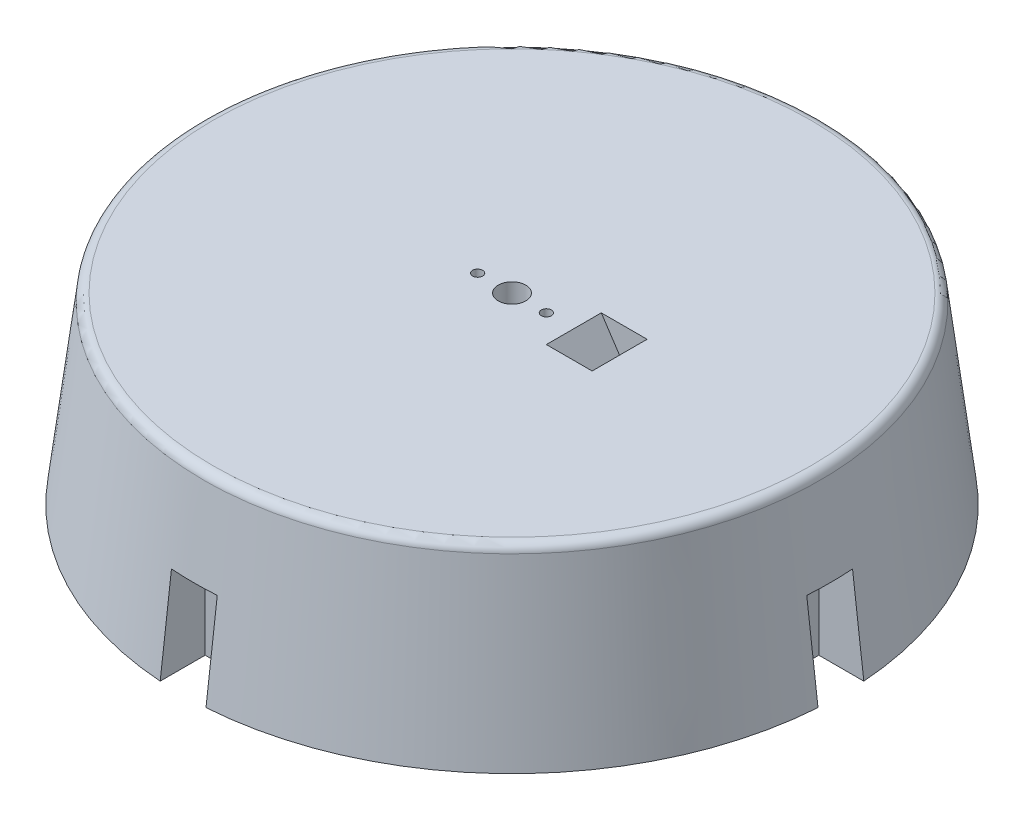
SolidWorks part; units mm, degrees
material "ABS PC"
ref_plane "Plan de face" through (0, 0, 0) normal (0, 0, 1) x (1, 0, 0)
ref_plane "Plan de dessus" through (0, 0, 0) normal (0, 1, 0) x (1, 0, 0)
ref_plane "Plan de droite" through (0, 0, 0) normal (1, 0, 0) x (0, 0, -1)
sketch "Esquisse3" plane through (0, 0, 0) normal (0, 1, 0) x (1, 0, 0)
  circle A0 centre (0, 0) radius 72
  dimension "D1" = 144
extrude "Boss.-Extru.1" add sketch "Esquisse3" along normal blind 40 draft 7
fillet "Congé2" radius 2 1 edges at (0, 40, 67.0886)
sketch "Esquisse26" plane through (0, 0, 0) normal (0, -1, 0) x (-1, 0, 0)
  circle A1 centre (0, 0) radius 20 construction
  circle A3 centre (0, 0) radius 7.5
  dimension "D1" = 40
  dimension "D4" = 15
extrude "Enlèv. mat.-Extru.1" cut sketch "Esquisse26" against normal blind 4
sketch "Esquisse27" [suppressed] plane through (0, 0, 0) normal (0, -1, 0) x (1, 0, 0)
  line L0 (0, 0) -> (84.4078, 0) construction
  line L1 (0, 0) -> (0, 67.4941) construction
  line L2 (99.7787, 6.6489) -> (93.792, 6.25)
  line L3 (99.7787, -6.6489) -> (93.792, -6.25)
  circle A0 centre (0, 0) radius 100 construction
  arc A1 (99.7787, -6.6489) -> (99.7787, 6.6489) centre (0, 0) ccw
  arc A2 (93.792, -6.25) -> (93.792, 6.25) centre (0, 0) ccw
  circle A4 centre (0, 0) radius 94 construction
  circle A5 centre (0, 0) radius 100 construction
  point P8 (52.5968, 16.0804)
  point P13 (52, 0)
  dimension "D2" = 12.5
  dimension "D1" = 6
extrude "Boss.-Extru.14" [suppressed] add sketch "Esquisse27" along normal blind 30
ref_plane "Plan1" [suppressed] through (93.792, 0, 0) normal (1, 0, 0) x (0, 0, -1)
sketch "Esquisse29" [suppressed] plane through (93.792, 0, 0) normal (1, 0, 0) x (0, 0, -1)
  line L0 (6.25, -30) -> (6.25, 0) construction
  line L1 (-6.25, -30) -> (-6.25, 0) construction
  line L2 (6.25, -24.317) -> (6.25, 0) construction
  line L3 (-6.25, -33.1717) -> (-6.25, 0) construction
  line L4 (-6.25, -30) -> (6.25, -30) construction
  line L5 (-6.25, -30) -> (6.25, -30) construction
  line L6 (0, -30) -> (0, -24.1817) construction
  circle A0 centre (0, -26) radius 4
  dimension "D1" = 8
extrude "Boss.-Extru.15" [suppressed] add sketch "Esquisse29" along normal blind 2 and the other way blind 8 draft 1
fillet "Congé7" [suppressed] radius 2
pattern_circular "Répétition circulaire4" [suppressed] count 4 over 360 of bodies 123
sketch "Esquisse39" plane through (0, 0, 0) normal (0, -1, 0) x (1, 0, 0)
  line L0 (0, 0) -> (72, 0) construction
  line L1 (72, -5) -> (72, 5)
  line L2 (72, 5) -> (62, 5)
  line L4 (72, -5) -> (62, -5)
  line L5 (62, 5) -> (62, -5)
  line L6 (72, 5) -> (62, -5) construction
  line L7 (72, -5) -> (62, 5) construction
  circle A0 centre (0, 0) radius 72 construction
  circle A2 centre (0, 0) radius 67 construction
  point P3 (67, 0)
  dimension "D2" = 134
  dimension "D1" = 10
extrude "Enlèv. mat.-Extru.4" cut sketch "Esquisse39" against normal blind 20
sketch "Esquisse40" plane through (62, 0, 0) normal (1, 0, 0) x (0, 0, -1)
  line L0 (0, 0) -> (0, 10) construction
  line L1 (-5, 0) -> (5, 0) construction
  line L2 (-5, 10) -> (5, 10) construction
  line L3 (-5, 20) -> (-5, 0) construction
  line L4 (5, 20) -> (5, 0) construction
  circle A0 centre (0, 5) radius 2.1643
  circle A1 centre (0, 15) radius 2.1643
hole_wizard "Dégagement M2.51" positions "Esquisse41" profile "Esquisse42" hole size "M2.5" standard "ISO"
sketch "Esquisse41" plane through (62, 0, 0) normal (1, 0, 0) x (0, 0, -1)
  point P0 (0, 15)
  point P3 (0, 5)
sketch "Esquisse42" plane through (62, 15, 0) normal (0, 1, 0) x (0, 0, -1)
  line L0 (0, 0) -> (0, 4.8112)
  line L1 (0, 4.8112) -> (1.35, 4)
  line L2 (1.35, 4) -> (1.35, 0)
  line L5 (1.35, 0) -> (0, 0)
  line L10 (0, 4.8112) -> (-1.35, 4) construction
  line L11 (0, -6.35) -> (0, 107.95) construction
  dimension "Diamètre du perçage" = 2.7
  dimension "Profondeur du perçage" = 4
  dimension "Angle de pointe" = 118
pattern_circular "Répétition circulaire5" count 4 every 90 about axis through (0, 4, 0) along (0, -1, 0) of "Enlèv. mat.-Extru.4", "Dégagement M2.51"
sketch "Esquisse30" plane through (0, 40, 0) normal (0, 1, 0) x (1, 0, 0)
  line L0 (0, 0) -> (0, 72.707) construction
  line L1 (0, 0) -> (85.5223, 0) construction
  line L2 (7.5, 0) -> (-7.5, 0)
  circle A0 centre (0, 0) radius 3
  dimension "D2" = 6
  dimension "D1" = 15
ref_axis "Axe1" through (0, 117.1902, 0) along (0, -1, 0)
hole_wizard "Dégagement M21" positions "Esquisse31" profile "Esquisse32" hole size "M2" standard "ISO"
sketch "Esquisse31" plane through (0, 40, 0) normal (0, 1, 0) x (1, 0, 0)
  line L2 (0, 0) -> (0, 24.4674) construction
  line L4 (-7.5, 0) -> (7.5, 0) construction
  point P29 (-7.5, 0)
  point P30 (7.5, 0)
  point P32 (0, 0)
  dimension "D1" = 15
sketch "Esquisse32" plane through (7.5, 40, 0) normal (1, 0, 0) x (0, 0, 1)
  line L0 (0, 0) -> (0, 7.6609)
  line L1 (0, 7.6609) -> (1.1, 7)
  line L2 (1.1, 7) -> (1.1, 0)
  line L5 (1.1, 0) -> (0, 0)
  line L10 (0, 7.6609) -> (-1.1, 7) construction
  line L11 (0, -6.35) -> (0, 107.95) construction
  dimension "Diamètre du perçage" = 2.2
  dimension "Profondeur du perçage" = 7
  dimension "Angle de pointe" = 118
extrude "Enlèv. mat.-Extru.2" cut sketch "Esquisse30" against normal blind 15 contours L2 A0 | L2 A0 region at (0, 40, 1.2732) region at (0, 40, -1.2732)
sketch "Esquisse33" plane through (0, 25, 0) normal (0, 1, 0) x (1, 0, 0)
  line L0 (0, 0) -> (0, 41.3983) construction
  circle A0 centre (0, 0) radius 2
  dimension "D1" = 4
extrude "Enlèv. mat.-Extru.3" cut sketch "Esquisse33" against normal through all
sketch "Esquisse34" plane through (0, 40, 0) normal (0, 1, 0) x (1, 0, 0)
  line L0 (0, 0) -> (65.3192, 0) construction
  line L1 (0, 0) -> (0, 65.3192) construction
  line L2 (13.5, 6) -> (13.5, -6)
  line L3 (13.5, -6) -> (23.5, -6)
  line L4 (23.5, -6) -> (23.5, 6)
  line L5 (23.5, 6) -> (13.5, 6)
  circle A0 centre (0, 0) radius 65.3192 construction
  point P11 (13.5, 0)
  dimension "D1" = 10
  dimension "D2" = 12
  dimension "D3" = 13.5
sketch "Esquisse36" plane through (0, 0, 0) normal (0, -1, 0) x (1, 0, 0)
  line L0 (0, 0) -> (40, 0) construction
  line L9 (50, -6) -> (50, 6)
  line L10 (40, -6) -> (50, -6)
  line L11 (40, 6) -> (40, -6)
  line L12 (50, 6) -> (40, 6)
  line L13 (13.5, -6) -> (13.5, 6) construction
  line L14 (13.5, 6) -> (23.5, 6) construction
  dimension "D1" = 40
ref_plane "Plan2" through (27.7989, 18.4168, 0) normal (0.8336, 0.5523, 0) x (0, 0, -1)
ref_plane "Plan3" through (34.7486, 23.021, 0) normal (-0.8336, -0.5523, 0) x (0, 0, 1)
sketch "Esquisse37" plane through (27.7989, 18.4168, 0) normal (0.8336, 0.5523, 0) x (0, 0, -1)
  line L1 (6, 25.89) -> (-6, 25.89) construction
  line L3 (6, 25.89) -> (-6, 25.89)
  line L4 (6, 25.89) -> (6, -22.0917)
  line L6 (-6, -22.0917) -> (6, -22.0917) construction
  line L7 (-6, -22.0917) -> (6, -22.0917)
  line L8 (-6, 25.89) -> (-6, -22.0917)
extrude "Passage de cable" cut sketch "Esquisse36" along direction (0.5523, -0.8336, 0) on the side against the normal through all
sketch "Esquisse38" plane through (0, 0, 0) normal (0, -1, 0) x (-1, 0, 0)
  line L0 (0, 0) -> (0, 56.7481) construction
  line L17 (17.8293, 2.8513) -> (6.7498, 4.9083)
  line L18 (4.9083, 6.7498) -> (2.8513, 17.8293)
  line L19 (-2.8513, 17.8293) -> (-4.9083, 6.7498)
  line L20 (-6.7498, 4.9083) -> (-17.8293, 2.8513)
  line L21 (-17.8293, -2.8513) -> (-6.7498, -4.9083)
  line L22 (-4.9083, -6.7498) -> (-2.8513, -17.8293)
  line L23 (2.8513, -17.8293) -> (4.9083, -6.7498)
  line L24 (6.7498, -4.9083) -> (17.8293, -2.8513)
  line L25 (17.8293, 2.8513) -> (6.7498, 4.9083)
  line L26 (4.9083, 6.7498) -> (2.8513, 17.8293)
  line L27 (-2.8513, 17.8293) -> (-4.9083, 6.7498)
  line L28 (-6.7498, 4.9083) -> (-17.8293, 2.8513)
  line L29 (-17.8293, -2.8513) -> (-6.7498, -4.9083)
  line L30 (-4.9083, -6.7498) -> (-2.8513, -17.8293)
  line L31 (2.8513, -17.8293) -> (4.9083, -6.7498)
  line L32 (6.7498, -4.9083) -> (17.8293, -2.8513)
  arc A16 (17.8293, -2.8513) -> (17.8293, 2.8513) centre (17.3, 0) ccw
  arc A17 (4.9083, 6.7498) -> (6.7498, 4.9083) centre (7.1697, 7.1697) ccw
  arc A18 (2.8513, 17.8293) -> (-2.8513, 17.8293) centre (0, 17.3) ccw
  arc A19 (-6.7498, 4.9083) -> (-4.9083, 6.7498) centre (-7.1697, 7.1697) ccw
  arc A20 (-17.8293, 2.8513) -> (-17.8293, -2.8513) centre (-17.3, 0) ccw
  arc A21 (-4.9083, -6.7498) -> (-6.7498, -4.9083) centre (-7.1697, -7.1697) ccw
  arc A22 (-2.8513, -17.8293) -> (2.8513, -17.8293) centre (0, -17.3) ccw
  arc A23 (6.7498, -4.9083) -> (4.9083, -6.7498) centre (7.1697, -7.1697) ccw
  arc A24 (17.8293, -2.8513) -> (17.8293, 2.8513) centre (17.3, 0) ccw
  arc A25 (4.9083, 6.7498) -> (6.7498, 4.9083) centre (7.1697, 7.1697) ccw
  arc A26 (2.8513, 17.8293) -> (-2.8513, 17.8293) centre (0, 17.3) ccw
  arc A27 (-6.7498, 4.9083) -> (-4.9083, 6.7498) centre (-7.1697, 7.1697) ccw
  arc A28 (-17.8293, 2.8513) -> (-17.8293, -2.8513) centre (-17.3, 0) ccw
  arc A29 (-4.9083, -6.7498) -> (-6.7498, -4.9083) centre (-7.1697, -7.1697) ccw
  arc A30 (-2.8513, -17.8293) -> (2.8513, -17.8293) centre (0, -17.3) ccw
  arc A31 (6.7498, -4.9083) -> (4.9083, -6.7498) centre (7.1697, -7.1697) ccw
  dimension "D1" = 0.7
extrude "Etoile" cut sketch "Esquisse38" against normal up to surface (4 mm away) up to face at (0, 4, -2)
